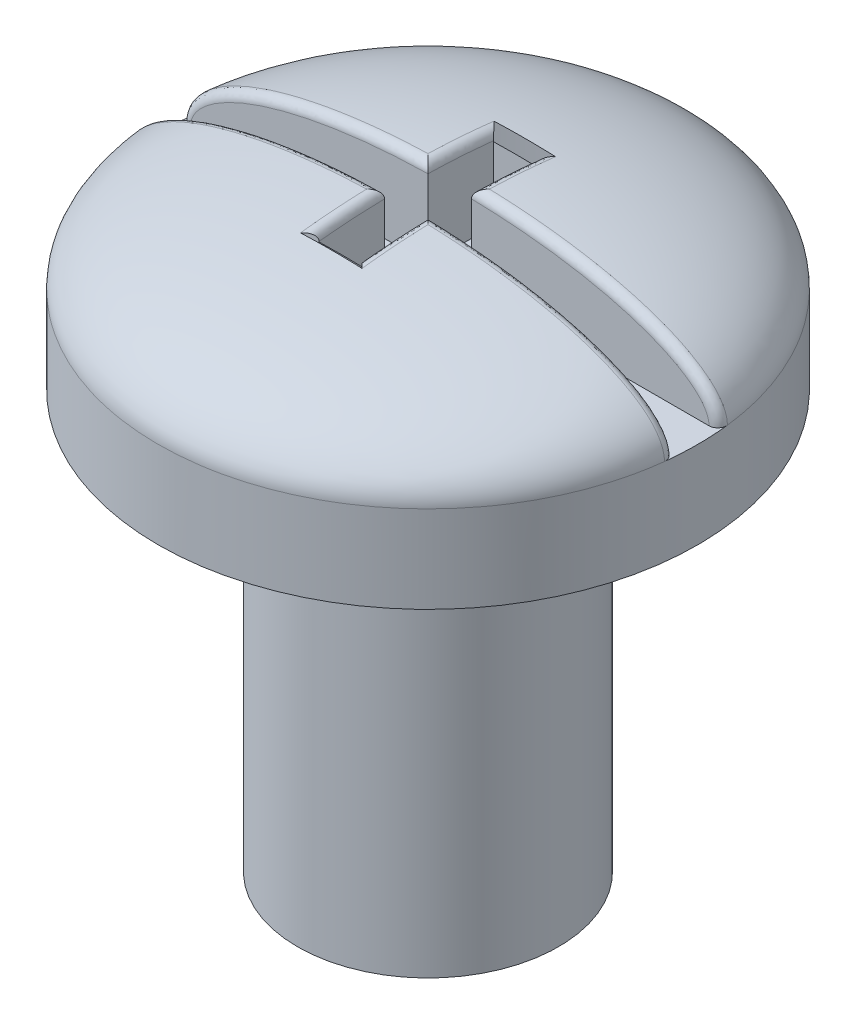
SolidWorks part; units mm, degrees
material "Stainless Steel (ferritic)"
ref_plane "Front Plane" through (0, 0, 0) normal (0, 0, 1) x (1, 0, 0)
ref_plane "Top Plane" through (0, 0, 0) normal (0, 1, 0) x (1, 0, 0)
ref_plane "Right Plane" through (0, 0, 0) normal (1, 0, 0) x (0, 0, -1)
sketch "Sketch1" plane through (0, 0, 0) normal (0, 1, 0) x (1, 0, 0)
  circle A0 centre (0, 0) radius 3.1
  dimension "D1" = 6.2
extrude "Boss-Extrude1" add sketch "Sketch1" along normal blind 0.9
sketch "Sketch3" plane through (0, 0.9, 0) normal (0, 1, 0) x (1, 0, 0)
  circle A0 centre (0, 0) radius 3.1
  dimension "D1" = 6.2
extrude "Boss-Extrude2" add sketch "Sketch3" along normal blind 1.1
fillet "Fillet1" radius 1 1 edges at (0, 2, 3.1) second distance 3 first distance on face at (0, 0, 3.1)
sketch "Sketch4" plane through (0, 2, 0) normal (0, 1, 0) x (1, 0, 0)
  line L0 (-3.5, 0) -> (3.5, 0) construction
  line L1 (0, 1) -> (0, -1) construction
  line L2 (-3.5, -0.25) -> (-0.25, -0.25)
  line L3 (-0.25, 1) -> (-0.25, 0.25)
  line L4 (-3.5, 0.25) -> (-0.25, 0.25)
  line L5 (0.25, 1) -> (0.25, 0.25)
  line L6 (0.25, 1) -> (-0.25, 1)
  line L7 (0.25, -1) -> (-0.25, -1)
  line L8 (3.5, 0.25) -> (3.5, -0.25)
  line L9 (-3.5, 0.25) -> (-3.5, -0.25)
  line L10 (0.25, 0.25) -> (3.5, 0.25)
  line L11 (-3.5, 0.25) -> (3.5, 0.25) construction
  line L12 (0.25, -0.25) -> (0.25, -1)
  line L13 (0.25, 1) -> (0.25, -1) construction
  line L14 (0.25, -0.25) -> (3.5, -0.25)
  line L15 (-3.5, -0.25) -> (3.5, -0.25) construction
  line L16 (-0.25, -0.25) -> (-0.25, -1)
  line L17 (-0.25, 1) -> (-0.25, -1) construction
  point P4 (0, 0)
  point P10 (0, 0)
  dimension "D1" = 7
  dimension "D2" = 2
  dimension "D3" = 0.25
  dimension "D4" = 0.25
extrude "Cut-Extrude1" cut sketch "Sketch4" against normal blind 1
fillet "Fillet2" radius 0.1 10 edges at (0.25, 1.9816, -0.6252) (-0.25, 1.9816, 0.6252) (2.1048, 1.7394, -0.25) (2.6982, 1.4932, 0.25) (0.25, 1.9815, 0.6258) (-2.1048, 1.7394, 0.25) (-2.6982, 1.4932, -0.25) (-0.25, 1.9815, -0.6258) (-0.0001, 1.9539, 1) (0.0001, 1.9539, -1)
sketch "Sketch5" plane through (0, 0, 0) normal (0, -1, 0) x (1, 0, 0)
  circle A0 centre (0, 0) radius 1.5
  dimension "D1" = 3
extrude "Boss-Extrude3" add sketch "Sketch5" along normal blind 4.8
